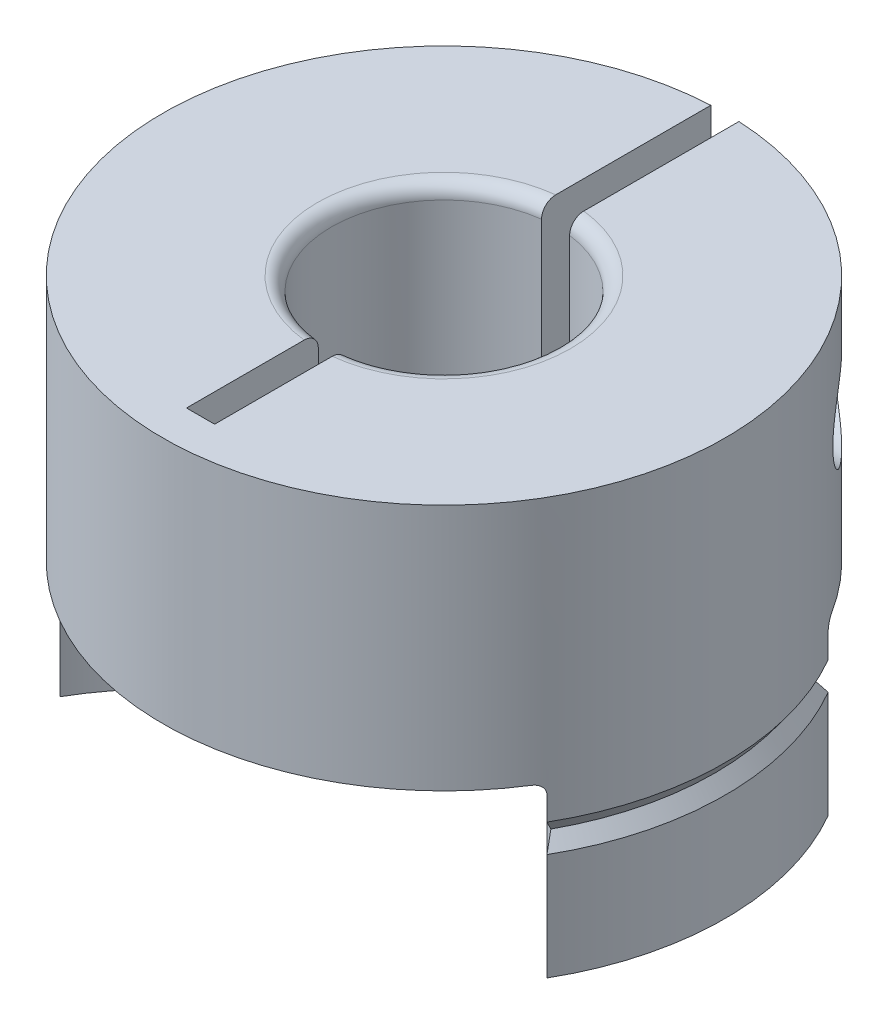
SolidWorks part; units mm, degrees
ref_plane "前视基准面" through (0, 0, 0) normal (0, 0, 1) x (1, 0, 0)
ref_plane "上视基准面" through (0, 0, 0) normal (0, 1, 0) x (1, 0, 0)
ref_plane "右视基准面" through (0, 0, 0) normal (1, 0, 0) x (0, 0, -1)
sketch "草图1" plane through (0, 0, 0) normal (0, 1, 0) x (1, 0, 0)
  line L0 (0, 0) -> (50000, 0) construction
  line L1 (0, 0) -> (0, 50000) construction
  line L2 (-5, 1.3397) -> (-5, -1.3397)
  line L3 (5, 1.3397) -> (5, -1.3397)
  circle A0 centre (0, 0) radius 10
  arc A1 (-8.6603, 5) -> (-5, 1.3397) centre (0, 10) ccw
  arc A2 (-8.6603, -5) -> (-5, -1.3397) centre (0, -10) cw
  arc A3 (5, -1.3397) -> (8.6603, -5) centre (0, -10) cw
  arc A4 (5, 1.3397) -> (8.6603, 5) centre (0, 10) ccw
  dimension "D1" = 20
  dimension "D2" = 10
  dimension "D3" = 10
extrude "凸台-拉伸1" add sketch "草图1" along normal blind 8.8 contours A0
extrude "凸台-拉伸2" add sketch "草图1<3>" against normal blind 6 contours A0 A2 L2 A1 | A4 L3 A3 A0 region at (-7.8135, 0, 0) region at (7.8135, 0, 0)
sketch "草图1<3>" plane through (0, 0, 0) normal (0, 1, 0) x (1, 0, 0) same geometry as "草图1"
sketch "草图2" plane through (0, 0, 0) normal (0, -1, 0) x (1, 0, 0)
  circle A0 centre (0, 0) radius 4
  dimension "D1" = 8
extrude "切除-拉伸1" cut sketch "草图2" against normal blind 10
sketch "草图3" plane through (0, 0, 0) normal (0, -1, 0) x (1, 0, 0)
  line L0 (0, 0) -> (0, 50000) construction
  line L1 (0, 0) -> (50000, 0) construction
  line L2 (-0.5, -3.9686) -> (-0.5, -9.9875)
  line L3 (0.5, -3.9686) -> (0.5, -9.9875)
  circle A0 centre (0, 0) radius 4 construction
  arc A1 (-8.6603, -5) -> (8.6603, -5) centre (0, 0) ccw construction
  arc A2 (-0.5, -3.9686) -> (0.5, -3.9686) centre (0, 0) ccw
  arc A3 (-0.5, -9.9875) -> (0.5, -9.9875) centre (0, 0) ccw
  dimension "D1" = 1
extrude "切除-拉伸2" cut sketch "草图3" against normal blind 10
ref_plane "基准面1" through (-3, 0, 0) normal (1, 0, 0) x (0, 0, -1)
sketch "草图4" plane through (-3, 0, 0) normal (1, 0, 0) x (0, 0, -1)
  line L0 (9.9875, 8.8) -> (-10, 8.8) construction
  line L1 (8.9875, 6.9) -> (8.9875, 3.1)
  line L3 (9.9875, 8.8) -> (9.9875, 0) construction
  arc A0 (8.9875, 6.9) -> (8.9875, 3.1) centre (6.9308, 5) ccw
  circle A1 centre (6.9308, 5) radius 1.5
  dimension "D1" = 5.6
  dimension "D3" = 3
  dimension "D2" = 3.8
  dimension "D4" = 3.8
  dimension "D5" = 1
extrude "切除-拉伸3" cut sketch "草图4" against normal blind 10 contours A0 L1
extrude "切除-拉伸4" cut sketch "草图4<3>" along normal blind 20 contours A1
sketch "草图4<3>" plane through (-3, 0, 0) normal (1, 0, 0) x (0, 0, -1) same geometry as "草图4"
sketch "草图5" plane through (0, 0, 0) normal (1, 0, 0) x (0, 0, -1)
  line L0 (-0.0063, 10) -> (-0.0063, 50010) construction
  line L1 (9.9875, 8.8) -> (-10, 8.8) construction
  line L2 (-8.6563, 8.8) -> (-0.0063, 8.8)
  line L4 (-0.0063, 8.8) -> (-0.0063, -0.4589)
  arc A0 (-0.0063, -0.4589) -> (-8.6563, 8.8) centre (3.9638, 11.9201) cw
  point P4 (-0.0063, 8.8)
  dimension "D1" = 13
  dimension "D2" = 8.65
extrude "切除-拉伸5" cut sketch "草图5" against normal mid plane 1 contours L2 L4 A0
sketch "草图6" plane through (0, 0, 0) normal (0, 0, 1) x (1, 0, 0)
  line L0 (-10, -1.7) -> (49990, -1.7) construction
  line L2 (10, 8.8) -> (-10, 8.8) construction
  line L3 (-10, -2.2) -> (-10, -1.2)
  line L4 (-10, 8.8) -> (-10, -6) construction
  line L5 (-10, -2.2) -> (-9.6367, -1.7)
  line L6 (-10, -1.2) -> (-9.6367, -1.7)
  line L7 (0, 10) -> (0, -49990) construction
  point P10 (-10, -1.7)
  point P12 (0, 8.8)
  dimension "D1" = 10.5
  dimension "D2" = 1
  dimension "D3" = 108
revolve "切除-旋转2" cut sketch "草图6" angle 360 about L7
fillet "圆角1" radius 0.35 6 edges at (7.0711, 0, 2.9289) (5, 0, 0) (7.0711, 0, -2.9289) (-7.0711, 0, 2.9289) (-5, 0, 0) (-7.0711, 0, -2.9289)
fillet "圆角2" radius 0.5 2 edges at (4, 8.8, 0) (-4, 8.8, 0)
fillet "圆角3" radius 0.5 1 edges at (0, 0, 4)
